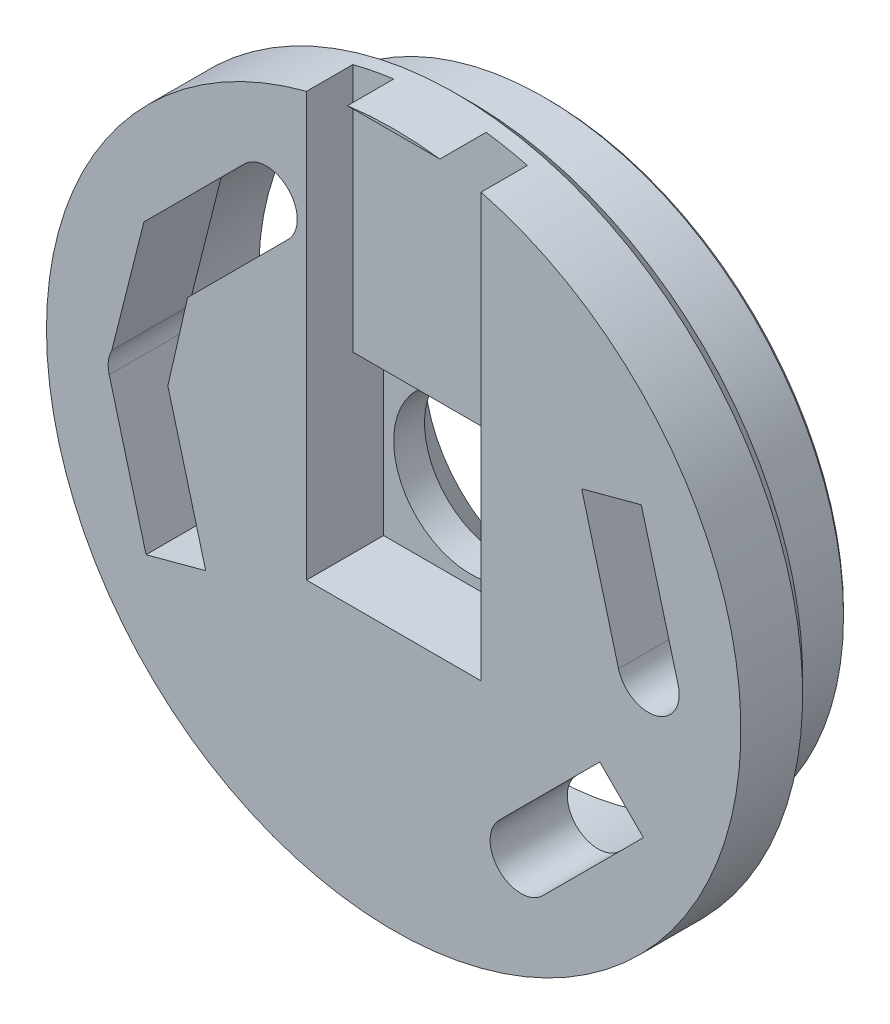
SolidWorks part; units mm, degrees
ref_plane "Front Plane" through (0, 0, 0) normal (0, 0, 1) x (1, 0, 0)
ref_plane "Top Plane" through (0, 0, 0) normal (0, 1, 0) x (1, 0, 0)
ref_plane "Right Plane" through (0, 0, 0) normal (1, 0, 0) x (0, 0, -1)
sketch "Sketch1" plane through (0, 0, 0) normal (0, 0, 1) x (1, 0, 0)
  circle A0 centre (0, 0) radius 9.8
  circle A1 centre (0, 0) radius 5
  dimension "D1" = 19.6
  dimension "D2" = 10
extrude "Boss-Extrude1" add sketch "Sketch1" along normal blind 10
sketch "Sketch2" plane through (0, 0, 10) normal (0, 0, 1) x (1, 0, 0)
  line L1 (-5.65, 5.65) -> (5.65, 5.65)
  line L2 (-5.65, 5.65) -> (-5.65, -5.65)
  line L3 (-5.65, -5.65) -> (5.65, -5.65)
  line L4 (5.65, 5.65) -> (5.65, -5.65)
  point P4 (5.65, 0)
  point P5 (0, 5.65)
  dimension "D1" = 11.3
  dimension "D2" = 11.3
extrude "Cut-Extrude1" cut sketch "Sketch2" against normal blind 5
sketch "Sketch3" plane through (0, 0, 10) normal (0, 0, 1) x (1, 0, 0)
  line L1 (-5.65, 5.65) -> (5.6634, 5.65)
  line L2 (-5.65, 5.65) -> (-5.65, 10.3571)
  line L3 (-5.65, 10.3571) -> (5.6634, 10.3571)
  line L4 (5.6634, 5.65) -> (5.6634, 10.3571)
extrude "Cut-Extrude2" cut sketch "Sketch3" against normal blind 3
sketch "Sketch4" plane through (0, 0, 10) normal (0, 0, 1) x (1, 0, 0)
  line L1 (-13.2922, 9.0382) -> (-7.8874, 9.0382)
  line L2 (-13.2922, 9.0382) -> (-13.2922, -9.0382)
  line L3 (-13.2922, -9.0382) -> (-7.8874, -9.0382)
  line L4 (-7.8874, 9.0382) -> (-7.8874, -9.0382)
  line L5 (13.4474, 9.0382) -> (7.784, 9.0382)
  line L6 (13.4474, 9.0382) -> (13.4474, -8.9089)
  line L7 (13.4474, -8.9089) -> (7.784, -8.9089)
  line L8 (7.784, 9.0382) -> (7.784, -8.9089)
extrude "Cut-Extrude3" cut sketch "Sketch4" against normal blind 3
chamfer "Chamfer1" distance 3 angle 45 1 edges at (5, 0, 0)
ref_plane "Plane1" through (0, 0, 5) normal (0, 0, -1) x (-1, 0, 0)
sketch "Sketch5" plane through (0, 0, 5) normal (0, 0, -1) x (-1, 0, 0)
  circle A0 centre (0, 0) radius 9.8
  circle A1 centre (0, 0) radius 22.5
  dimension "D1" = 12.7
extrude "Boss-Extrude2" add sketch "Sketch5" against normal blind 1
sketch "Sketch6" plane through (0, 0, 5) normal (0, 0, -1) x (-1, 0, 0)
  circle A0 centre (0, 0) radius 9.8
  circle A1 centre (0, 0) radius 11.25
  dimension "D1" = 22.5
extrude "Boss-Extrude3" add sketch "Sketch6" along normal up to surface (5 mm away) up to face at (8, 0, 0)
sketch "Sketch7" plane through (0, 0, 5) normal (0, 0, -1) x (-1, 0, 0)
  circle A0 centre (0, 0) radius 18.75
  circle A1 centre (0, 0) radius 19.4
  dimension "D1" = 37.5
  dimension "D2" = 38.8
extrude "Boss-Extrude4" add sketch "Sketch7" along normal up to surface (5 mm away) up to face at (8, 0, 0)
chamfer "Chamfer2" distance 0.25 angle 45 1 edges at (19.4, 0, 0)
sketch "Sketch9" plane through (0, 0, 6) normal (0, 0, 1) x (1, 0, 0)
  circle A0 centre (0, 0) radius 22.5
  circle A1 centre (0, 0) radius 9.8
  circle A2 centre (0, 0) radius 9.8 construction
  circle A3 centre (0, 0) radius 22.5 construction
extrude "Boss-Extrude5" add sketch "Sketch9" along normal up to surface (4 mm away) up to face at (1.1075, 1.2261, 10)
sketch "Sketch10" plane through (0, 0, 10) normal (0, 0, 1) x (1, 0, 0)
  line L1 (-5.65, 5.65) -> (5.6634, 5.65)
  line L2 (-5.65, 5.65) -> (-5.65, 22.3)
  line L3 (-5.65, 22.3) -> (5.6634, 22.3)
  line L4 (5.6634, 5.65) -> (5.6634, 22.3)
extrude "Cut-Extrude5" cut sketch "Sketch10" against normal up to surface (3 mm away) up to face at (1.1357, 6.9505, 7)
sketch "Sketch8" plane through (0, 0, 5) normal (0, 0, -1) x (-1, 0, 0)
  line L3 (-7.7324, 12.3576) -> (1.1726, 14.7437)
  line L4 (1.1726, 14.7437) -> (0.1374, 18.6074)
  line L5 (0.1374, 18.6074) -> (-8.7676, 16.2213)
  arc A1 (-7.7324, 12.3576) -> (-8.7676, 16.2213) centre (-8.25, 14.2894) cw
extrude "Cut-Extrude4" cut sketch "Sketch8" against normal through all
ref_axis "Axis1" through (0, 0, 10.5849) along (0, 0, -1)
pattern_circular "CirPattern1" count 6 over 360 about axis through (0, 0, 10.5849) along (0, 0, -1) of "Cut-Extrude4"
sketch "Sketch12" plane through (0, 0, 7) normal (0, 0, 1) x (1, 0, 0)
  line L1 (-9.9396, 6.8335) -> (-7.0029, 6.8335)
  line L2 (-9.9396, 6.8335) -> (-9.9396, -6.3817)
  line L3 (-9.9396, -6.3817) -> (-7.0029, -6.3817)
  line L4 (-7.0029, 6.8335) -> (-7.0029, -6.3817)
  line L5 (6.8899, 6.9464) -> (10.222, 6.9464)
  line L6 (6.8899, 6.9464) -> (6.8899, -6.3817)
  line L7 (6.8899, -6.3817) -> (10.222, -6.3817)
  line L8 (10.222, 6.9464) -> (10.222, -6.3817)
extrude "Boss-Extrude6" add sketch "Sketch12" along normal up to surface (3 mm away) up to face at (11.1559, -11.3835, 10)
chamfer "Chamfer3" distance 1 angle 45 1 edges at (-22.5, 0, 5)
sketch "Sketch13" plane through (0, 0, 10) normal (0, 0, 1) x (1, 0, 0)
  line L0 (-16.1831, 9.1847) -> (-18.5, 0)
  line L1 (-18.5, 0) -> (-14.6389, 0.7323)
  line L2 (-14.6389, 0.7323) -> (-13.3547, 6.3563)
  line L3 (-13.3547, 6.3563) -> (-16.1831, 9.1847)
  arc A0 (-14.5682, 0.5176) -> (-18.4319, -0.5177) centre (-16.5, 0) ccw construction
extrude "Cut-Extrude6" cut sketch "Sketch13" against normal blind 10
sketch "Sketch14" plane through (0, 0, 7) normal (0, 0, 1) x (1, 0, 0)
  line L0 (-0.1374, 18.6074) -> (5.6634, 17.0531)
  line L1 (5.6634, 17.0531) -> (5.6634, 12.912)
  line L2 (5.6634, 12.912) -> (-1.1726, 14.7437)
  line L3 (-1.1726, 14.7437) -> (-0.1374, 18.6074)
extrude "Boss-Extrude7" add sketch "Sketch14" against normal up to surface (2 mm away) up to face at (-13.8888, 2.9422, 5)
sketch "Sketch15" plane through (0, 0, 10) normal (0, 0, 1) x (1, 0, 0)
  line L0 (8.7676, 16.2213) -> (5.6634, 17.0531)
  line L1 (5.6634, 17.0531) -> (5.6634, 12.912)
  line L2 (5.6634, 12.912) -> (7.7324, 12.3576)
  arc A0 (7.7324, 12.3576) -> (8.7676, 16.2213) centre (8.25, 14.2894) ccw
extrude "Boss-Extrude8" add sketch "Sketch15" against normal up to surface (5 mm away) up to face at (-21.5, 0, 5)
sketch "Sketch16" plane through (0, 0, 10) normal (0, 0, 1) x (1, 0, 0)
  line L0 (-8.7676, -16.2213) -> (0.1374, -18.6074)
  line L1 (0.1374, -18.6074) -> (1.1726, -14.7437)
  line L2 (1.1726, -14.7437) -> (-7.7324, -12.3576)
  arc A0 (-7.7324, -12.3576) -> (-8.7676, -16.2213) centre (-8.25, -14.2894) ccw
extrude "Boss-Extrude9" add sketch "Sketch16" against normal up to surface (5 mm away) up to face at (-21.5, 0, 5)
